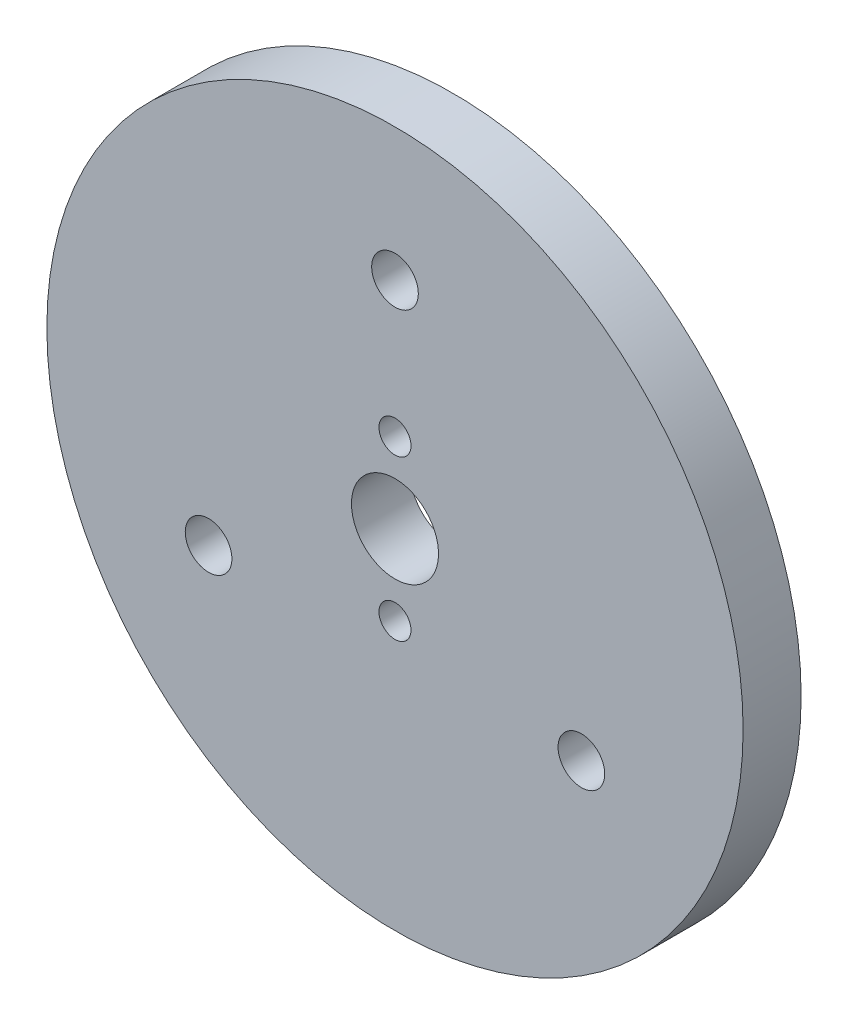
SolidWorks part; units mm, degrees
ref_plane "Front Plane" through (0, 0, 0) normal (0, 0, 1) x (1, 0, 0)
ref_plane "Top Plane" through (0, 0, 0) normal (0, 1, 0) x (1, 0, 0)
ref_plane "Right Plane" through (0, 0, 0) normal (1, 0, 0) x (0, 0, -1)
sketch "Sketch1" plane through (0, 0, 0) normal (0, 0, 1) x (1, 0, 0)
  circle A0 centre (0, 0) radius 38.1
  dimension "D1" = 76.2
extrude "Boss-Extrude1" add sketch "Sketch1" along normal blind 6.35
sketch "Sketch2" plane through (0, 0, 6.35) normal (0, 0, 1) x (1, 0, 0)
  circle A0 centre (0, 23.5585) radius 1.3525
  dimension "D1" = 23.5585
  dimension "D2" = 2.7051
extrude "Cut-Extrude1" cut sketch "Sketch2" against normal through all contours A0
sketch "Sketch3" plane through (0, 0, 0) normal (0, 0, -1) x (-1, 0, 0)
  circle A0 centre (0, 0) radius 4.7625
  dimension "D1" = 9.525
extrude "Cut-Extrude2" cut sketch "Sketch3" against normal blind 6.35
ref_axis "Axis1" through (0, 0, -0.3175) along (0, 0, 1)
pattern_circular "CirPattern2" count 3 over 360 about axis through (0, 0, -0.3175) along (0, 0, 1) of "Cut-Extrude1"
sketch "Sketch5" plane through (0, 0, 0) normal (0, 0, -1) x (-1, 0, 0)
  circle A0 centre (0, 8.7376) radius 1.7526
  dimension "D1" = 3.5052
  dimension "D2" = 8.7376
extrude "Cut-Extrude4" cut sketch "Sketch5" against normal blind 6.35
pattern_circular "CirPattern3" count 2 over 360 about axis through (0, 0, -0.3175) along (0, 0, 1) of "Cut-Extrude4"
hole_wizard "#10 Clearance Hole1" positions "Sketch6" profile "Sketch7" hole size "#10" standard "ANSI Inch"
sketch "Sketch6" plane through (0, 0, 0) normal (0, 0, -1) x (-1, 0, 0)
  point P0 (0, 23.5585)
  point P3 (-20.4023, -11.7792)
  point P6 (20.4023, -11.7793)
sketch "Sketch7" plane through (0, 23.5585, 0) normal (1, 0, 0) x (0, 1, 0)
  line L0 (0, 0) -> (0, 12.9638)
  line L1 (0, 12.9638) -> (2.5527, 11.43)
  line L2 (2.5527, 11.43) -> (2.5527, 0)
  line L5 (2.5527, 0) -> (0, 0)
  line L10 (0, 12.9638) -> (-2.5527, 11.43) construction
  line L11 (0, -6.35) -> (0, 107.95) construction
  dimension "Hole Dia." = 5.1054
  dimension "Hole Depth" = 11.43
  dimension "Drill Angle" = 118
